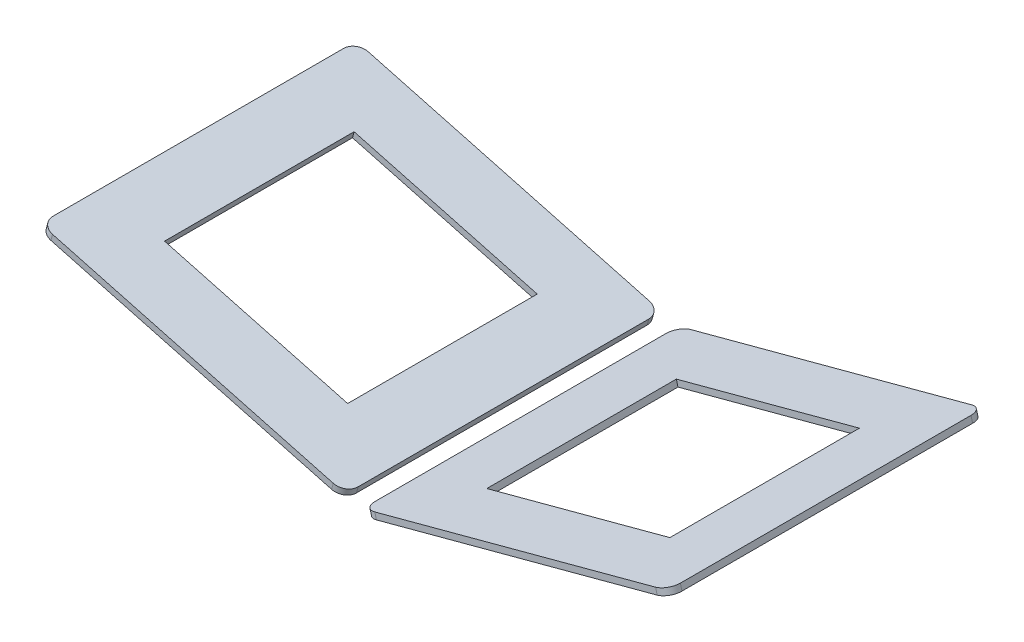
SolidWorks part; units mm, degrees
note: '?' marks a value the reader was unsure of.
ref_plane "前视基准面" through (0, 0, 0) normal (0, 0, 1) x (1, 0, 0)
ref_plane "上视基准面" through (0, 0, 0) normal (0, 1, 0) x (1, 0, 0)
ref_plane "右视基准面" through (0, 0, 0) normal (1, 0, 0) x (0, 0, -1)
sketch "草图1" plane through (0, 0, 0) normal (0, 1, 0) x (1, 0, 0)
  line L0 (-42, 15.3215) -> (-12, 15.3215)
  line L1 (-50, 25.3215) -> (-4, 25.3215)
  line L2 (-52, 23.3215) -> (-52, -22.6785)
  line L3 (-50, -24.6785) -> (-4, -24.6785)
  line L4 (-2, 23.3215) -> (-2, -22.6785)
  line L9 (-12, 15.3215) -> (-12, -14.6785)
  line L10 (-42, -14.6785) -> (-12, -14.6785)
  line L11 (-42, 15.3215) -> (-42, -14.6785)
  arc A0 (-52, 23.3215) -> (-50, 25.3215) centre (-50, 23.3215) cw
  arc A1 (-4, -24.6785) -> (-2, -22.6785) centre (-4, -22.6785) ccw
  arc A2 (-4, 25.3215) -> (-2, 23.3215) centre (-4, 23.3215) cw
  arc A7 (-52, -22.6785) -> (-50, -24.6785) centre (-50, -22.6785) ccw
  arc A8 (-12, 15.3215) -> (-12, 15.3215) centre (-12, 15.3215) cw
  arc A9 (-12, -14.6785) -> (-12, -14.6785) centre (-12, -14.6785) ccw
  arc A10 (-42, -14.6785) -> (-42, -14.6785) centre (-42, -14.6785) ccw
  arc A11 (-42, 15.3215) -> (-42, 15.3215) centre (-42, 15.3215) cw
  point P11 (-52, 25.3215)
  point P26 (-52, -24.6785)
  point P39 (0, 0)
  dimension "D4" = 2
  dimension "D5" = 2
  dimension "D1" = 50
  dimension "D7" = 10
extrude "凸台-拉伸1" add sketch "草图1" along normal blind 1
ref_axis "基准轴1" through (0, 0, 0) along (0, 0, 1)?
move or copy body "实体-移动/复制1" bodies to move or copy 106 copy no rotation origin (0, 0, 0) rotation axis (0, 0, -1) rotation angle 15
sketch "草图2" plane through (0, 0, 0) normal (0, 0, 1) x (1, 0, 0)
  line L0 (-49.9693, 14.4245) -> (-40.3101, 11.8363)
  line L1 (-40.3101, 11.8363) -> (-40.5689, 10.8704)
  line L2 (-40.5689, 10.8704) -> (-50.2281, 13.4586)
  line L3 (-50.2281, 13.4586) -> (-49.9693, 14.4245)
  point P3 (0, 0)
  point P6 (0, 0)
  point P8 (0, 0)
surface "曲面-基准面1" sketch "草图2"
ref_axis "基准轴2" through (0, 0, 0) along (0, 1, 0)?
pattern_circular "阵列(圆周)1" count 2 every 180 about axis through (0, 0, 0) along (0, 1, 0) of bodies 110 108
